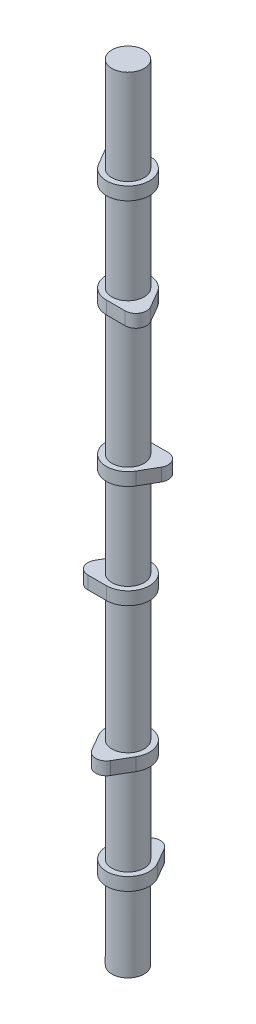
SolidWorks part; units mm, degrees
ref_plane "Front Plane" through (0, 0, 0) normal (0, 0, 1) x (1, 0, 0)
ref_plane "Top Plane" through (0, 0, 0) normal (0, 1, 0) x (1, 0, 0)
ref_plane "Right Plane" through (0, 0, 0) normal (1, 0, 0) x (0, 0, -1)
sketch "Sketch2" plane through (0, 0, 0) normal (0, 1, 0) x (1, 0, 0)
  line L0 (-5.4993, 15.875) -> (-10.9985, 6.35)
  line L1 (5.4993, 15.875) -> (10.9985, 6.35)
  arc A0 (-10.9985, 6.35) -> (10.9985, 6.35) centre (0, 0) ccw
  arc A1 (5.4993, 15.875) -> (-5.4993, 15.875) centre (0, 12.7) ccw
  dimension "D1" = 12.7
  dimension "D3" = 25.4
  dimension "D2" = 12.7
extrude "Boss-Extrude1" add sketch "Sketch2" along normal mid plane 7.62
ref_axis "Axis1" through (0, 261.8592, 0) along (0, -1, 0)
move or copy body "Body-Move/Copy1" bodies to move or copy 101 copy yes number of copies 1 translate (0, 60.96, 0) parameters "D1"=0, "D2"=0, "D3"=0
move or copy body "Body-Move/Copy2" bodies to move or copy 113 copy no rotation origin (0, 0, 0) rotation axis (0, 1, 0) rotation angle 180
sketch "Sketch3" plane through (0, 0, 0) normal (0, 1, 0) x (1, 0, 0)
  circle A0 centre (0, 0) radius 9.5
  dimension "D1" = 19
extrude "Boss-Extrude2" add sketch "Sketch3" along normal blind 146.05 from offset 25.4 offset against normal yes
pattern_linear "LPattern1" count 3 spacing 146.05 along (0, 1, 0) of bodies 115
move or copy body "Body-Move/Copy3" bodies to move or copy 116 copy no rotation origin (0, 0, 0) rotation axis (0, 1, 0) rotation angle 120
move or copy body "Body-Move/Copy4" bodies to move or copy 117 copy no rotation origin (0, 0, 0) rotation axis (0, -1, 0) rotation angle 120
sketch "Sketch4" plane through (0, -25.4, 0) normal (0, -1, 0) x (1, 0, 0)
  circle A0 centre (0, 0) radius 9.5
extrude "Boss-Extrude3" add sketch "Sketch4" along normal blind 24.94
combine bodies "Combine1" operation type add bodies to combine 119 118 120
equation "\"59.63.00mm\"=60"
